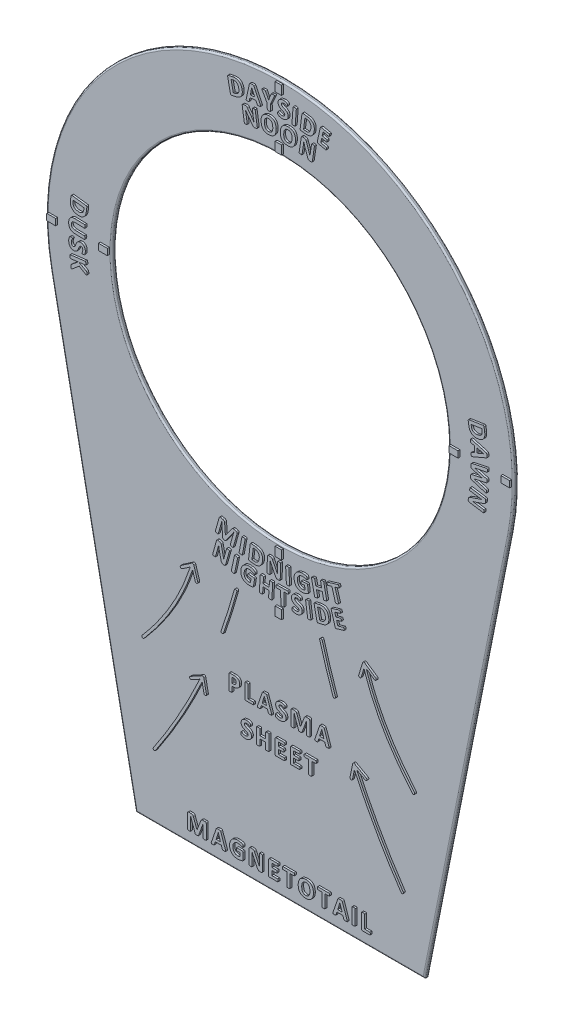
SolidWorks part; units mm, degrees
ref_plane "Front Plane" through (0, 0, 0) normal (0, 0, 1) x (1, 0, 0)
ref_plane "Top Plane" through (0, 0, 0) normal (0, 1, 0) x (1, 0, 0)
ref_plane "Right Plane" through (0, 0, 0) normal (1, 0, 0) x (0, 0, -1)
sketch "Body Sketch" plane through (0, 0, 0) normal (0, 0, 1) x (1, 0, 0)
  line L0 (49.0562, -153.0394) -> (-49.0562, -153.0394) construction
  line L1 (-49.0562, -153.0394) -> (-76.4501, -15.1927) construction
  line L2 (49.0562, -153.0394) -> (76.4501, -15.1927) construction
  line L3 (45.7729, -149.0394) -> (-45.7729, -149.0394) construction
  line L4 (-45.7729, -149.0394) -> (-72.5268, -14.4131) construction
  line L5 (45.7729, -149.0394) -> (72.5268, -14.4131) construction
  line L6 (45.3625, -148.5394) -> (72.0364, -14.3156)
  line L7 (-45.3625, -148.5394) -> (-72.0364, -14.3156)
  line L8 (45.3625, -148.5394) -> (-45.3625, -148.5394)
  arc A0 (76.4501, -15.1927) -> (-76.4501, -15.1927) centre (0, 0) ccw construction
  arc A1 (72.5268, -14.4131) -> (-72.5268, -14.4131) centre (0, 0) ccw construction
  circle A2 centre (0, 0) radius 52.5 construction
  arc A3 (72.0364, -14.3156) -> (-72.0364, -14.3156) centre (0, 0) ccw
  circle A4 centre (0, 0) radius 53
  dimension "D1" = 105
extrude "Main Body" add sketch "Body Sketch" against normal blind 1.4
fillet "Top & Bottom Fillet" radius 0.5 10 edges at (53, 0, 0) (58.6994, -81.4275, 0) (0, 73.4451, 0) (-58.6994, -81.4275, 0) (0, -148.5394, 0) (53, 0, -1.4) (-58.6994, -81.4275, -1.4) (0, 73.4451, -1.4) (58.6994, -81.4275, -1.4) (0, -148.5394, -1.4)
sketch "Inner Shelf Guide" plane through (0, 0, 0) normal (0, 0, 1) x (1, 0, 0)
  line L0 (-4.8897, 26.045) -> (-6.8064, 23.9948) construction
  line L1 (0, 0) -> (0, -50.2) construction
  line L2 (4.8897, 26.045) -> (7.4916, 27.0104) construction
  line L3 (4.8897, 26.045) -> (6.8064, 23.9948) construction
  line L4 (5.6066, 25.6443) -> (6.9891, 24.1655)
  line L5 (5.7959, 26.1146) -> (7.5785, 26.776)
  line L6 (4.7071, 25.8742) -> (6.6238, 23.8241)
  line L7 (4.8028, 26.2794) -> (7.4046, 27.2448)
  line L8 (-4.8897, 26.045) -> (-7.4916, 27.0104) construction
  line L9 (-4.8028, 26.2794) -> (-7.4046, 27.2448)
  line L10 (-4.7071, 25.8742) -> (-6.6238, 23.8241)
  line L11 (-5.7959, 26.1146) -> (-7.5785, 26.776)
  line L12 (-5.6066, 25.6443) -> (-6.9891, 24.1655)
  line L13 (0, 50.2) -> (0, -50.2) construction
  line L14 (0, 50.2) -> (0, 47.2) construction
  line L15 (-1, 47.2) -> (1, 47.2)
  line L16 (1, 47.2) -> (1, 50)
  line L17 (1, 50) -> (-1, 50)
  line L19 (-1, 50) -> (-1, 47.2)
  line L24 (50, -1) -> (50, 1)
  line L25 (47.2, 1) -> (47.2, -1)
  line L26 (47.2, -1) -> (50, -1)
  line L27 (50, 1) -> (47.2, 1)
  line L28 (-1, -50) -> (1, -50)
  line L29 (1, -47.2) -> (-1, -47.2)
  line L30 (-1, -47.2) -> (-1, -50)
  line L31 (1, -50) -> (1, -47.2)
  line L32 (-50, 1) -> (-50, -1)
  line L33 (-47.2, -1) -> (-47.2, 1)
  line L34 (-47.2, 1) -> (-50, 1)
  line L35 (-50, -1) -> (-47.2, -1)
  line L36 (0, 0) -> (-50.2, 0) construction
  line L37 (0, 0) -> (50.7, 0) construction
  line L38 (-15.981, -37.7572) -> (-12.1456, -36.7236) construction
  line L39 (-14.6921, -38.2772) -> (-15.981, -37.7572) construction
  line L40 (-15.981, -37.7572) -> (-13.8857, -41.2242) construction
  line L41 (-17.83, 36.9266) -> (-19.5817, 33.3615) construction
  line L42 (-16.5801, -38.1193) -> (-14.4848, -41.5863)
  line L43 (-17.7072, 37.6157) -> (-21.6954, 38.3264)
  line L44 (-16.1632, -37.0813) -> (-12.3278, -36.0477)
  line L45 (-18.4506, 36.6139) -> (-17.83, 36.9266) construction
  line L46 (-17.83, 36.9266) -> (-21.8182, 37.6372) construction
  line L47 (-17.2017, 36.6179) -> (-18.9535, 33.0528)
  line L48 (-13.7513, -37.8813) -> (-11.9635, -37.3995)
  line L49 (-19.9843, 36.5994) -> (-21.941, 36.9481)
  line L50 (-14.3108, -39.1675) -> (-13.2866, -40.8622)
  line L51 (-19.3969, 35.3249) -> (-20.21, 33.6702)
  arc A0 (-23.5365, -12.1717) -> (-13.8449, -22.5927) centre (0, 0) ccw construction
  arc A1 (12.6832, -23.2648) -> (13.8449, -22.5927) centre (0, 0) ccw construction
  circle A2 centre (0, 0) radius 50.2 construction
  arc A3 (0.4875, -23.3949) -> (0.4875, 23.3949) centre (0, 0) ccw construction
  arc A4 (12.5524, 23.3386) -> (4.8897, 26.045) centre (0, 0) ccw construction
  arc A5 (-12.6832, -23.2648) -> (-13.8449, -22.5927) centre (0, 0) cw construction
  arc A6 (12.5636, -23.0453) -> (13.7143, -22.3796) centre (0, 0) ccw
  arc A7 (12.8029, -23.4843) -> (13.9756, -22.8059) centre (0, 0) ccw
  arc A8 (13.7143, -22.3796) -> (13.9756, -22.8059) centre (13.8449, -22.5927) cw
  arc A9 (7.3358, -49.2049) -> (7.8212, -49.0851) centre (7.5785, -49.145) ccw
  arc A10 (-23.7585, -12.2865) -> (-13.9756, -22.8059) centre (0, 0) ccw
  arc A11 (-12.8029, -23.4843) -> (-13.9756, -22.8059) centre (0, 0) cw
  arc A12 (6.9891, 24.1655) -> (6.6238, 23.8241) centre (6.8064, 23.9948) cw
  arc A13 (-23.3144, -12.0568) -> (-13.7143, -22.3796) centre (0, 0) ccw
  arc A14 (7.4046, 27.2448) -> (7.5785, 26.776) centre (7.4916, 27.0104) cw
  arc A15 (-12.5636, -23.0453) -> (-13.7143, -22.3796) centre (0, 0) cw
  arc A16 (12.6708, 23.5587) -> (5.7959, 26.1146) centre (0, 0) ccw
  arc A17 (-23.7585, -12.2865) -> (-23.3144, -12.0568) centre (-23.5365, -12.1717) cw
  arc A18 (-7.8212, -49.0851) -> (-7.3358, -49.2049) centre (-7.5785, -49.145) ccw
  arc A19 (12.434, 23.1184) -> (5.6066, 25.6443) centre (0, 0) ccw
  arc A20 (12.6708, 23.5587) -> (12.434, 23.1184) centre (12.5524, 23.3386) cw
  arc A21 (-4.8897, 26.045) -> (-23.1368, 12.9204) centre (0, 0) ccw construction
  arc A22 (4.8028, 26.2794) -> (4.7071, 25.8742) centre (4.8897, 26.045) ccw
  arc A23 (-23.3551, 13.0423) -> (-22.9185, 12.7985) centre (-23.1368, 12.9204) ccw
  arc A24 (-6.9891, 24.1655) -> (-6.6238, 23.8241) centre (-6.8064, 23.9948) ccw
  arc A25 (-4.8028, 26.2794) -> (-4.7071, 25.8742) centre (-4.8897, 26.045) cw
  arc A26 (-7.4046, 27.2448) -> (-7.5785, 26.776) centre (-7.4916, 27.0104) ccw
  arc A27 (-5.7959, 26.1146) -> (-23.3551, 13.0423) centre (0, 0) ccw
  arc A28 (-5.6066, 25.6443) -> (-22.9185, 12.7985) centre (0, 0) ccw
  arc A29 (-0.4875, 23.3949) -> (-0.4875, -23.3949) centre (0, 0) ccw construction
  arc A30 (-44.6, 0) -> (0, -44.6) centre (0, 0) ccw construction
  arc A32 (-18.4506, 36.6139) -> (-35.1983, -21.0257) centre (0, 0) ccw construction
  arc A33 (37.8, 0) -> (-37.8, 0) centre (0, 0) ccw construction
  arc A34 (-14.6921, -38.2772) -> (17.8274, 36.9213) centre (0, 0) ccw construction
  arc A35 (-13.7513, -37.8813) -> (17.523, 36.291) centre (0, 0) ccw
  arc A36 (-14.3108, -39.1675) -> (18.1317, 37.5517) centre (0, 0) ccw
  arc A37 (-11.9635, -37.3995) -> (-12.3278, -36.0477) centre (-12.1456, -36.7236) ccw
  arc A38 (17.523, 36.291) -> (18.1317, 37.5517) centre (17.8274, 36.9213) cw
  arc A39 (-35.7992, -21.3847) -> (-34.5973, -20.6668) centre (-35.1983, -21.0257) ccw
  arc A40 (-16.5801, -38.1193) -> (-16.1632, -37.0813) centre (-15.981, -37.7572) cw
  arc A41 (-20.21, 33.6702) -> (-18.9535, 33.0528) centre (-19.5817, 33.3615) ccw
  arc A42 (-17.7072, 37.6157) -> (-17.2017, 36.6179) centre (-17.83, 36.9266) cw
  arc A43 (-21.6954, 38.3264) -> (-21.941, 36.9481) centre (-21.8182, 37.6372) ccw
  arc A44 (-19.9843, 36.5994) -> (-35.7992, -21.3847) centre (0, 0) ccw
  arc A45 (-19.3969, 35.3249) -> (-34.5973, -20.6668) centre (0, 0) ccw
  arc A46 (-14.4848, -41.5863) -> (-13.2866, -40.8622) centre (-13.8857, -41.2242) ccw
  spline S0 degree 3 poles (-12.6832, -23.2648) (-12.3563, -23.443) (-8.9855, -25.7063) (-5.7868, -35.6805) (-6.3061, -43.9891) (-7.5785, -49.145) knots 0 0 0 0 0.03888 0.448269 1 1 1 1 construction
  spline S1 degree 3 poles (12.6832, -23.2648) (12.3563, -23.443) (8.9855, -25.7063) (5.7868, -35.6805) (6.3061, -43.9891) (7.5785, -49.145) knots 0 0 0 0 0.03888 0.448269 1 1 1 1 construction
  spline S2 degree 3 poles (12.5636, -23.0453) (12.3006, -23.1887) (11.7874, -23.5186) (10.8988, -24.2419) (9.5191, -25.7322) (8.0803, -28.3376) (6.9957, -31.8876) (6.1607, -36.661) (6.0284, -41.1774) (6.5001, -45.1556) (6.9255, -47.4503) (7.1927, -48.6249) (7.3358, -49.2049) knots 0 0 0 0 0.03125 0.0625 0.125 0.25 0.375 0.5 0.75 0.875 0.9375 1 1 1 1
  spline S3 degree 3 poles (12.8029, -23.4843) (12.3202, -23.7474) (11.4231, -24.4101) (9.942, -26.0129) (8.5454, -28.5271) (7.4848, -31.9974) (6.8664, -35.5347) (6.5927, -38.9282) (6.6634, -42.2802) (6.9949, -45.0814) (7.4152, -47.3487) (7.6796, -48.5113) (7.8212, -49.0851) knots 0 0 0 0 0.0625 0.125 0.25 0.375 0.5 0.625 0.75 0.875 0.9375 1 1 1 1
  spline S4 degree 3 poles (-12.8029, -23.4843) (-12.3202, -23.7474) (-11.4231, -24.4101) (-9.942, -26.0129) (-8.5454, -28.5271) (-7.4848, -31.9974) (-6.8664, -35.5347) (-6.5927, -38.9282) (-6.6634, -42.2802) (-6.9949, -45.0814) (-7.4152, -47.3487) (-7.6796, -48.5113) (-7.8212, -49.0851) knots 0 0 0 0 0.0625 0.125 0.25 0.375 0.5 0.625 0.75 0.875 0.9375 1 1 1 1
  spline S5 degree 3 poles (-12.5636, -23.0453) (-12.3006, -23.1887) (-11.7874, -23.5186) (-10.8988, -24.2419) (-9.5191, -25.7322) (-8.0803, -28.3376) (-6.9957, -31.8876) (-6.1607, -36.661) (-6.0284, -41.1774) (-6.5001, -45.1556) (-6.9255, -47.4503) (-7.1927, -48.6249) (-7.3358, -49.2049) knots 0 0 0 0 0.03125 0.0625 0.125 0.25 0.375 0.5 0.75 0.875 0.9375 1 1 1 1
  point P82 (0, 47.2)
  point P102 (-15.981, -37.7572)
  point P108 (0, 0)
  dimension "D1" = 23.4
sketch "Text Sketch" plane through (0, 0, 0) normal (0, 0, 1) x (1, 0, 0)
  line L0 (0, 72.9451) -> (0, 53.5) construction
  line L1 (-1, 72.7451) -> (1, 72.7451)
  line L2 (-1, 72.7451) -> (-1, 69.9451)
  line L3 (-1, 69.9451) -> (1, 69.9451)
  line L4 (1, 69.9451) -> (1, 72.7451)
  line L5 (0, 63.2225) -> (-1, 63.2225) construction
  line L6 (-1, 56.5) -> (1, 56.5)
  line L7 (1, 56.5) -> (1, 53.7)
  line L8 (-1, 53.7) -> (-1, 56.5)
  line L9 (-1, 53.7) -> (1, 53.7)
  line L10 (72.7451, 1) -> (72.7451, -1)
  line L11 (72.7451, 1) -> (69.9451, 1)
  line L12 (69.9451, 1) -> (69.9451, -1)
  line L13 (69.9451, -1) -> (72.7451, -1)
  line L14 (56.5, 1) -> (56.5, -1)
  line L15 (56.5, -1) -> (53.7, -1)
  line L16 (53.7, 1) -> (56.5, 1)
  line L17 (53.7, 1) -> (53.7, -1)
  line L18 (63.2225, 0) -> (63.2225, 1) construction
  line L21 (69.9451, 0) -> (56.5, 0) construction
  line L22 (1, -56.5) -> (-1, -56.5)
  line L23 (-1, -56.5) -> (-1, -53.7)
  line L24 (1, -53.7) -> (1, -56.5)
  line L25 (1, -53.7) -> (-1, -53.7)
  line L26 (-72.7451, -1) -> (-72.7451, 1)
  line L27 (-72.7451, -1) -> (-69.9451, -1)
  line L28 (-69.9451, -1) -> (-69.9451, 1)
  line L29 (-69.9451, 1) -> (-72.7451, 1)
  line L30 (-56.5, -1) -> (-56.5, 1)
  line L31 (-56.5, 1) -> (-53.7, 1)
  line L32 (-53.7, -1) -> (-56.5, -1)
  line L33 (-53.7, -1) -> (-53.7, 1)
  line L34 (1, -72.7451) -> (-1, -72.7451) [skipped]
  line L35 (1, -72.7451) -> (1, -69.9451) [skipped]
  line L36 (1, -69.9451) -> (-1, -69.9451) [skipped]
  line L37 (-1, -69.9451) -> (-1, -72.7451) [skipped]
  line L38 (72.9451, 0) -> (53.5, 0) construction
  line L39 (0, -63.2225) -> (1, -63.2225) construction
  line L40 (0, -72.9451) -> (0, -53.5) construction
  line L41 (-63.2225, 0) -> (-63.2225, -1) construction
  line L42 (-72.9451, 0) -> (-53.5, 0) construction
  line L43 (-1, -69.9451) -> (1, -69.9451)
  line L44 (1, -69.9451) -> (1, -72.7451)
  line L45 (-1, -72.7451) -> (-1, -69.9451)
  line L46 (-1, -72.7451) -> (1, -72.7451)
  line L47 (0, -148.0394) -> (0, -72.9451) construction
  line L48 (-44.9521, -148.0394) -> (44.9521, -148.0394) construction
  line L49 (30, -144.6418) -> (-30, -144.6418) construction
  line L50 (0, -72.9451) -> (0, -139.1513) construction
  line L51 (0, -106.0482) -> (2.1276, -106.0482) construction
  line L52 (-20, -100.3147) -> (20, -100.3147) construction
  line L53 (-20, -110.6475) -> (20, -110.6475) construction
  arc A0 (71.546, -14.2182) -> (-71.546, -14.2182) centre (0, 0) ccw construction
  arc A1 (71.546, -14.2182) -> (-71.546, -14.2182) centre (0, 0) ccw construction
  circle A2 centre (0, 0) radius 53.5 construction
  circle A3 centre (0, 0) radius 53.5 construction
  arc A4 (20.7982, 53.6068) -> (-20.7982, 53.6068) centre (0, 0) ccw construction
  arc A5 (34.5032, 53.7842) -> (-34.5032, 53.7842) centre (0, 0) ccw construction
  arc A6 (-61.5696, 23.3539) -> (-61.5696, -23.3539) centre (0, 0) ccw construction
  arc A7 (57.0662, -20.6868) -> (57.0662, 20.6868) centre (0, 0) ccw construction
  arc A8 (-35.9562, -58.891) -> (35.9562, -58.891) centre (0, 0) ccw construction
  arc A9 (-24.4478, -57.4114) -> (24.4478, -57.4114) centre (0, 0) ccw construction
  arc A11 (62.4, 0) -> (-62.4, 0) centre (0, 0) ccw construction
  text T0 "DAYSIDE" font "Calibri" height 5
  text T1 "NOON" font "Calibri" height 5
  text T2 "DAWN" font "Calibri" height 5
  text T3 "DUSK" font "Calibri" height 5
  text T4 "NIGHTSIDE" font "Calibri" height 5
  text T5 "MIDNIGHT" font "Calibri" height 5
  text T6 "MAGNETOTAIL" font "Calibri" height 5
  text T7 "PLASMA" font "Calibri" height 5
  text T8 "SHEET" font "Calibri" height 5
  point P9 (0, 72.7451)
  point P18 (0, -72.7451)
  point P23 (72.7451, 0)
  point P41 (-72.7451, 0)
  point P48 (0, 0)
  point P79 (0, 0)
  point P94 (0, -144.6418)
  point P101 (0, -100.3147)
  point P104 (0, -110.6475)
  dimension "D1" = 0.2
  dimension "D5" = 63.9
  dimension "D6" = 57.5
  dimension "D7" = 60.7
  dimension "D8" = 4
  dimension "D9" = 131.7
  dimension "D10" = 138
  dimension "D11" = 62.4
  dimension "D2" = 2.8
  dimension "D3" = 2
  dimension "D4" = 4
extrude "Text" add sketch "Text Sketch" along normal blind 0.6
sketch "Lines Sketch" plane through (0, 0, 0) normal (0, 0, 1) x (1, 0, 0)
  line L0 (24.4443, -102.2347) -> (23.7762, -100.7899) construction
  line L1 (26.9154, -71.7029) -> (27.5966, -73.7521) construction
  line L2 (-23.7762, -100.7899) -> (-27.4763, -102.8194) construction
  line L3 (-23.7762, -100.7899) -> (-22.9422, -104.9269) construction
  line L4 (26.9154, -71.7029) -> (25.6747, -75.7365) construction
  line L5 (26.9154, -71.7029) -> (30.3957, -74.0898) construction
  line L6 (-26.9154, -71.7029) -> (-30.3957, -74.0898) construction
  line L7 (23.7762, -100.7899) -> (22.9422, -104.9269) construction
  line L8 (23.7762, -100.7899) -> (27.4763, -102.8194) construction
  line L9 (-26.9154, -71.7029) -> (-25.6747, -75.7365) construction
  line L10 (-26.9154, -71.7029) -> (-27.5966, -73.7521) construction
  line L11 (-24.4443, -102.2347) -> (-23.7762, -100.7899) construction
  line L12 (0, -148.0394) -> (0, 0) construction
  line L13 (24.0812, -102.4026) -> (23.9266, -102.0681)
  line L14 (-23.9685, -100.4392) -> (-27.6687, -102.4687)
  line L15 (24.6493, -101.7251) -> (27.284, -103.1701)
  line L16 (24.8074, -102.0668) -> (24.6493, -101.7251)
  line L17 (23.3841, -100.7109) -> (22.5501, -104.8478)
  line L18 (23.9685, -100.4392) -> (27.6687, -102.4687)
  line L19 (23.9266, -102.0681) -> (23.3343, -105.0059)
  line L20 (23.4916, -100.1776) -> (27.6687, -102.4687) construction
  line L21 (23.4916, -100.1776) -> (22.5501, -104.8478) construction
  line L22 (24.0812, -102.4026) -> (23.4131, -100.9578) construction
  line L23 (26.5331, -71.5853) -> (25.2923, -75.6189)
  line L24 (-44.9521, -148.0394) -> (44.9521, -148.0394) construction
  line L25 (24.0608, -101.4022) -> (23.3343, -105.0059) construction
  line L26 (24.0608, -101.4022) -> (27.284, -103.1701) construction
  line L27 (-27.1417, -71.373) -> (-30.622, -73.76)
  line L28 (24.8074, -102.0668) -> (24.1392, -100.622) construction
  line L29 (-24.0812, -102.4026) -> (-23.9266, -102.0681)
  line L31 (27.1417, -71.373) -> (30.622, -73.76)
  line L32 (27.6702, -72.7056) -> (27.9761, -73.626)
  line L33 (27.6702, -72.7056) -> (30.1695, -74.4197)
  line L34 (27.295, -71.5767) -> (27.9761, -73.626) construction
  line L35 (26.9302, -73.0154) -> (26.057, -75.8541)
  line L36 (-23.3841, -100.7109) -> (-22.5501, -104.8478)
  line L37 (26.9302, -73.0154) -> (27.217, -73.8783)
  line L38 (-24.8074, -102.0668) -> (-24.6493, -101.7251)
  line L40 (26.5358, -71.829) -> (27.217, -73.8783) construction
  line L41 (-24.6493, -101.7251) -> (-27.284, -103.1701)
  line L42 (-24.8074, -102.0668) -> (-24.1392, -100.622) construction
  line L43 (-23.9266, -102.0681) -> (-23.3343, -105.0059)
  line L44 (-24.0812, -102.4026) -> (-23.4131, -100.9578) construction
  line L46 (-26.5331, -71.5853) -> (-25.2923, -75.6189)
  line L48 (-26.9302, -73.0154) -> (-27.217, -73.8783)
  line L49 (-26.9302, -73.0154) -> (-26.057, -75.8541)
  line L50 (-26.5358, -71.829) -> (-27.217, -73.8783) construction
  line L53 (-27.6702, -72.7056) -> (-30.1695, -74.4197)
  line L56 (-27.6702, -72.7056) -> (-27.9761, -73.626)
  line L58 (-27.295, -71.5767) -> (-27.9761, -73.626) construction
  arc A0 (13.028, -72.1266) -> (13.7991, -71.9134) centre (13.4136, -72.02) cw
  arc A1 (17.221, -85.5022) -> (17.9755, -85.2363) centre (17.5983, -85.3692) ccw
  arc A2 (23.3841, -100.7109) -> (23.9685, -100.4392) centre (23.7762, -100.7899) cw
  arc A3 (38.5909, -128.1129) -> (39.2538, -127.6652) centre (38.9223, -127.8891) ccw
  arc A4 (23.3343, -105.0059) -> (22.5501, -104.8478) centre (22.9422, -104.9269) cw
  arc A5 (27.284, -103.1701) -> (27.6687, -102.4687) centre (27.4763, -102.8194) ccw
  arc A6 (-13.7991, -71.9134) -> (-13.028, -72.1266) centre (-13.4136, -72.02) cw
  arc A7 (42.1897, -99.3739) -> (42.7955, -98.8515) centre (42.4926, -99.1127) ccw
  arc A8 (-17.9755, -85.2363) -> (-17.221, -85.5022) centre (-17.5983, -85.3692) ccw
  arc A9 (25.2923, -75.6189) -> (26.057, -75.8541) centre (25.6747, -75.7365) ccw
  arc A10 (26.5331, -71.5853) -> (27.1417, -71.373) centre (26.9154, -71.7029) cw
  arc A11 (30.1695, -74.4197) -> (30.622, -73.76) centre (30.3957, -74.0898) ccw
  arc A13 (-27.6687, -102.4687) -> (-27.284, -103.1701) centre (-27.4763, -102.8194) ccw
  arc A14 (-30.622, -73.76) -> (-30.1695, -74.4197) centre (-30.3957, -74.0898) ccw
  arc A15 (-23.3343, -105.0059) -> (-22.5501, -104.8478) centre (-22.9422, -104.9269) ccw
  arc A16 (-38.5909, -128.1129) -> (-39.2538, -127.6652) centre (-38.9223, -127.8891) cw
  arc A17 (-23.3841, -100.7109) -> (-23.9685, -100.4392) centre (-23.7762, -100.7899) ccw
  arc A19 (-26.057, -75.8541) -> (-25.2923, -75.6189) centre (-25.6747, -75.7365) ccw
  arc A20 (-27.1417, -71.373) -> (-26.5331, -71.5853) centre (-26.9154, -71.7029) cw
  arc A21 (-42.7955, -98.8515) -> (-42.1897, -99.3739) centre (-42.4926, -99.1127) ccw
  spline S0 degree 3 poles (13.4136, -72.02) (13.6109, -72.7335) (14.8745, -77.2211) (16.2937, -81.6672) (17.5983, -85.3692) knots 0.276962 0.276962 0.276962 0.276962 0.303018 0.441046 0.441046 0.441046 0.441046 construction
  spline S1 degree 3 poles (27.5966, -73.7521) (30.7356, -83.1964) (35.9771, -91.5563) (42.4926, -99.1127) knots 0.041793 0.041793 0.041793 0.041793 1 1 1 1 construction
  spline S2 degree 2 poles (24.4443, -102.2347) (30.6321, -115.6154) (38.9223, -127.8891) knots 0.654453 0.654453 0.654453 1 1 1 construction
  spline S3 degree 2 poles (-24.4443, -102.2347) (-30.6321, -115.6154) (-38.9223, -127.8891) knots 0.654453 0.654453 0.654453 1 1 1 construction
  spline S4 degree 3 poles (-27.5966, -73.7521) (-30.7356, -83.1964) (-35.9771, -91.5563) (-42.4926, -99.1127) knots 0.041793 0.041793 0.041793 0.041793 1 1 1 1 construction
  spline S5 degree 3 poles (-13.4136, -72.02) (-13.6109, -72.7335) (-14.8745, -77.2211) (-16.2937, -81.6672) (-17.5983, -85.3692) knots 0.276962 0.276962 0.276962 0.276962 0.303018 0.441046 0.441046 0.441046 0.441046 construction
  spline S6 degree 1 poles (13.028, -72.1266) (17.221, -85.5022) knots 0 0 1 1 construction
  spline S7 degree 3 poles (13.028, -72.1266) (14.2733, -76.63) (15.6681, -81.0953) (17.221, -85.5022) knots 0.276962 0.276962 0.276962 0.276962 0.441046 0.441046 0.441046 0.441046
  spline S8 degree 1 poles (24.0812, -102.4026) (38.5909, -128.1129) knots 0 0 1 1 construction
  spline S9 degree 3 poles (24.0812, -102.4026) (26.1458, -106.8669) (30.6302, -115.6232) (35.8314, -124.0275) (38.5909, -128.1129) knots 0.654453 0.654453 0.654453 0.654453 0.827227 1 1 1 1
  spline S10 degree 1 poles (13.7991, -71.9134) (17.9755, -85.2363) knots 0 0 1 1 construction
  spline S11 degree 3 poles (13.7991, -71.9134) (15.0395, -76.3991) (16.4287, -80.8468) (17.9755, -85.2363) knots 0.276962 0.276962 0.276962 0.276962 0.441046 0.441046 0.441046 0.441046
  spline S12 degree 1 poles (24.8074, -102.0668) (39.2538, -127.6652) knots 0 0 1 1 construction
  spline S13 degree 3 poles (24.8074, -102.0668) (26.8628, -106.5116) (31.3276, -115.2295) (36.5063, -123.5975) (39.2538, -127.6652) knots 0.654453 0.654453 0.654453 0.654453 0.827227 1 1 1 1
  spline S14 degree 1 poles (27.217, -73.8783) (42.1897, -99.3739) knots 0 0 1 1 construction
  spline S15 degree 3 poles (27.217, -73.8783) (28.0006, -76.2359) (29.8529, -80.8773) (33.3296, -87.4044) (37.4386, -93.578) (40.5628, -97.4871) (42.1897, -99.3739) knots 0.041793 0.041793 0.041793 0.041793 0.281345 0.520896 0.760448 1 1 1 1
  spline S16 degree 1 poles (27.9761, -73.626) (42.7955, -98.8515) knots 0 0 1 1 construction
  spline S17 degree 3 poles (27.9761, -73.626) (28.7502, -75.9549) (30.5793, -80.5382) (34.0169, -86.9925) (38.0839, -93.1036) (41.1827, -96.981) (42.7955, -98.8515) knots 0.041793 0.041793 0.041793 0.041793 0.281345 0.520896 0.760448 1 1 1 1
  spline S18 degree 1 poles (-13.7991, -71.9134) (-17.9755, -85.2363) knots 0 0 1 1 construction
  spline S19 degree 3 poles (-13.7991, -71.9134) (-15.0395, -76.3991) (-16.4287, -80.8468) (-17.9755, -85.2363) knots 0.276962 0.276962 0.276962 0.276962 0.441046 0.441046 0.441046 0.441046
  spline S20 degree 1 poles (-24.0812, -102.4026) (-38.5909, -128.1129) knots 0 0 1 1 construction
  spline S21 degree 3 poles (-38.5909, -128.1129) (-35.8314, -124.0275) (-30.6302, -115.6232) (-26.1458, -106.8669) (-24.0812, -102.4026) knots 0.654453 0.654453 0.654453 0.654453 0.827227 1 1 1 1
  spline S22 degree 1 poles (-13.028, -72.1266) (-17.221, -85.5022) knots 0 0 1 1 construction
  spline S23 degree 3 poles (-13.028, -72.1266) (-14.2733, -76.63) (-15.6681, -81.0953) (-17.221, -85.5022) knots 0.276962 0.276962 0.276962 0.276962 0.441046 0.441046 0.441046 0.441046
  spline S24 degree 1 poles (-24.8074, -102.0668) (-39.2538, -127.6652) knots 0 0 1 1 construction
  spline S25 degree 3 poles (-39.2538, -127.6652) (-36.5063, -123.5975) (-31.3276, -115.2295) (-26.8628, -106.5116) (-24.8074, -102.0668) knots 0.654453 0.654453 0.654453 0.654453 0.827227 1 1 1 1
  spline S26 degree 1 poles (-27.9761, -73.626) (-42.7955, -98.8515) knots 0 0 1 1 construction
  spline S27 degree 3 poles (-27.9761, -73.626) (-28.7502, -75.9549) (-30.5793, -80.5382) (-34.0169, -86.9925) (-38.0839, -93.1036) (-41.1827, -96.981) (-42.7955, -98.8515) knots 0.041793 0.041793 0.041793 0.041793 0.281345 0.520896 0.760448 1 1 1 1
  spline S28 degree 1 poles (-27.217, -73.8783) (-42.1897, -99.3739) knots 0 0 1 1 construction
  spline S29 degree 3 poles (-27.217, -73.8783) (-28.0006, -76.2359) (-29.8529, -80.8773) (-33.3296, -87.4044) (-37.4386, -93.578) (-40.5628, -97.4871) (-42.1897, -99.3739) knots 0.041793 0.041793 0.041793 0.041793 0.281345 0.520896 0.760448 1 1 1 1
  point P0 (26.5358, -71.829)
  point P7 (23.9541, -101.1726)
  point P12 (23.1872, -104.9763)
  point P20 (27.3561, -103.0386)
  point P21 (24.6712, -102.1297)
  point P23 (24.0812, -102.4026)
  point P24 (24.0031, -100.685)
  point P25 (23.4131, -100.9578)
  point P26 (26.9434, -72.5935)
  point P27 (23.5983, -100.4072)
  point P28 (22.6971, -104.8775)
  point P29 (27.5966, -102.6002)
  point P30 (24.2174, -102.3396)
  point P32 (23.5493, -100.8949)
  point P34 (27.217, -73.8783)
  point P36 (24.0608, -101.4022)
  point P37 (26.6778, -71.7805)
  point P41 (27.0544, -72.1013)
  point P42 (25.9136, -75.81)
  point P43 (30.2543, -74.296)
  point P44 (27.4187, -72.4382)
  point P45 (27.1531, -71.6252)
  point P49 (26.7764, -71.3044)
  point P50 (25.4357, -75.663)
  point P51 (30.5371, -73.8837)
  point P52 (26.6892, -72.0327)
  point P57 (23.3343, -105.0059)
  point P58 (27.284, -103.1701)
  point P61 (30.1695, -74.4197)
  point P63 (24.8074, -102.0668)
  point P64 (24.1392, -100.622)
  point P66 (27.295, -71.5767)
  point P67 (27.9761, -73.626)
  point P68 (23.4916, -100.1776)
  point P69 (22.5501, -104.8478)
  point P70 (27.6687, -102.4687)
  point P74 (27.2977, -71.8205)
  point P75 (26.057, -75.8541)
  point P99 (26.6892, -72.0327)
  point P106 (27.2977, -71.8205)
  point P114 (-24.1683, -100.869)
  point P120 (-27.2977, -71.8205)
  point P125 (-23.5838, -101.1406)
  point P137 (-26.6892, -72.0327)
  dimension "D2" = 0.4
extrude "Lines" add sketch "Lines Sketch" along normal blind 0.6
